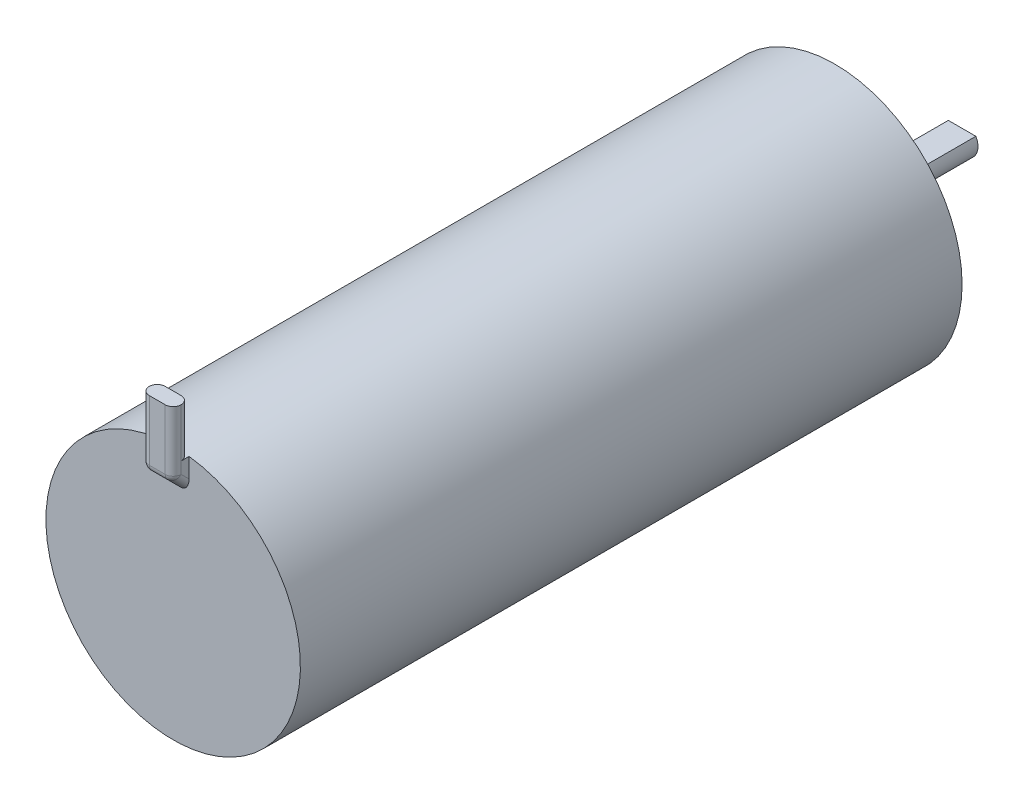
SolidWorks part; units mm, degrees
material "AISI 316 Annealed Stainless Steel Bar (SS)"
ref_plane "Ön Düzlem" through (0, 0, 0) normal (0, 0, 1) x (1, 0, 0)
ref_plane "Üst Düzlem" through (0, 0, 0) normal (0, 1, 0) x (1, 0, 0)
ref_plane "Sağ Düzlem" through (0, 0, 0) normal (1, 0, 0) x (0, 0, -1)
sketch "Sketch1" plane through (0, 0, 0) normal (0, 0, 1) x (1, 0, 0)
  circle A0 centre (0, 0) radius 8
extrude "Boss-Extrude1" add sketch "Sketch1" along normal blind 41.6
sketch "Sketch2" plane through (0, 0, 41.6) normal (0, 0, 1) x (1, 0, 0)
  line L1 (-1, 11) -> (1, 11)
  line L2 (-1, 11) -> (-1, 6)
  line L3 (-1, 6) -> (1, 6)
  line L4 (1, 11) -> (1, 6)
  circle A0 centre (0, 0) radius 8 construction
  dimension "D1" = 2
  dimension "D2" = 1
  dimension "D3" = 6
  dimension "D4" = 5
extrude "Boss-Extrude2" add sketch "Sketch2" along normal blind 1
chamfer "Chamfer1" distance 1 angle 45 1 edges at (0, 6, 42.6)
fillet "Fillet1" radius 0.5 5 edges at (0, 7, 42.6) (1, 6.5, 42.1) (1, 9, 42.6) (-1, 6.5, 42.1) (-1, 9, 42.6)
fillet "Fillet2" radius 0.5 2 edges at (-1, 9.4686, 41.6) (1, 9.4686, 41.6)
sketch "Sketch3" plane through (0, 0, 0) normal (0, 0, -1) x (-1, 0, 0)
  circle A0 centre (0, 0) radius 1
extrude "Boss-Extrude3" add sketch "Sketch3" along normal blind 8
sketch "Sketch4" plane through (0, 0, -8) normal (0, 0, -1) x (-1, 0, 0)
  line L1 (-1.2872, 1.8879) -> (1.4953, 1.8879)
  line L2 (-1.2872, 1.8879) -> (-1.2872, 0.5)
  line L3 (-1.2872, 0.5) -> (1.4953, 0.5)
  line L4 (1.4953, 1.8879) -> (1.4953, 0.5)
  dimension "D1" = 0.5
extrude "Cut-Extrude1" cut sketch "Sketch4" against normal blind 4
